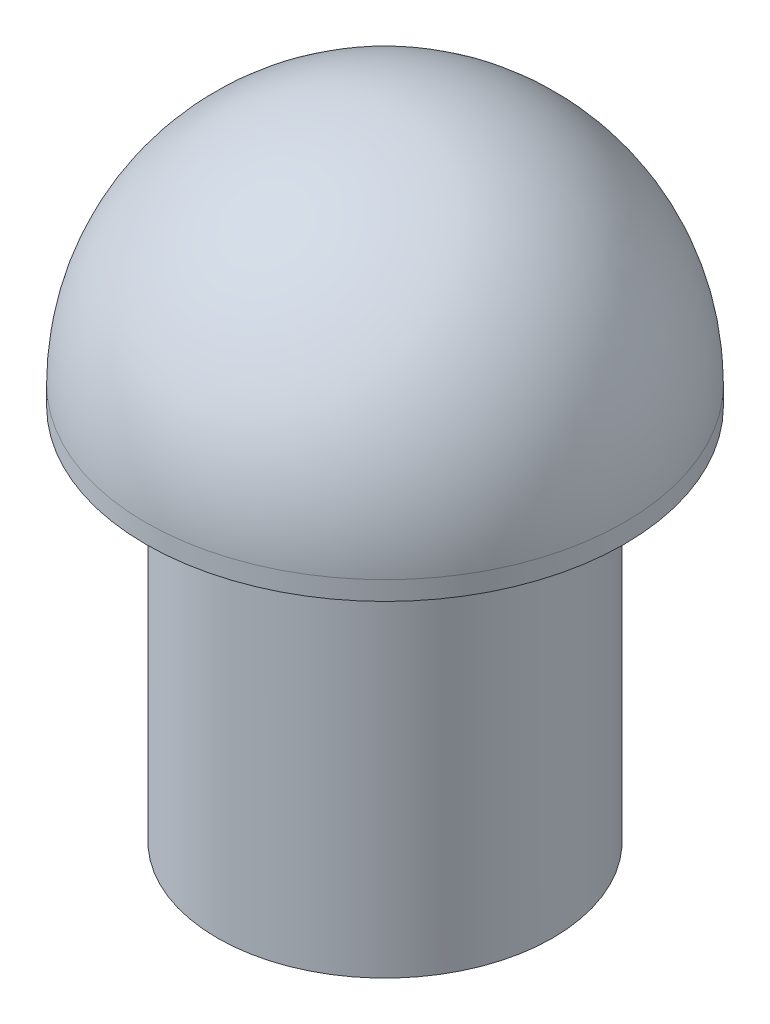
SolidWorks part; units mm, degrees
ref_plane "Front Plane" through (0, 0, 0) normal (0, 0, 1) x (1, 0, 0)
ref_plane "Top Plane" through (0, 0, 0) normal (0, 1, 0) x (1, 0, 0)
ref_plane "Right Plane" through (0, 0, 0) normal (1, 0, 0) x (0, 0, -1)
sketch "Sketch1" plane through (0, 0, 0) normal (0, 1, 0) x (1, 0, 0)
  circle A0 centre (0, 0) radius 6.35
extrude "Boss-Extrude1" add sketch "Sketch1" along normal blind 0.5
dome "Dome1" faces to dome 1 distance 6.35 reverse direction no elliptical dome no face at (0, 0.5, 6.35) parameters "D1"=6.35
sketch "Sketch2" plane through (0, 0, 0) normal (0, -1, 0) x (1, 0, 0)
  circle A0 centre (0, 0) radius 4.45
  circle A1 centre (0, 0) radius 3
  dimension "D1" = 8.9
  dimension "D2" = 6
extrude "Boss-Extrude2" add sketch "Sketch2" along normal blind 10
